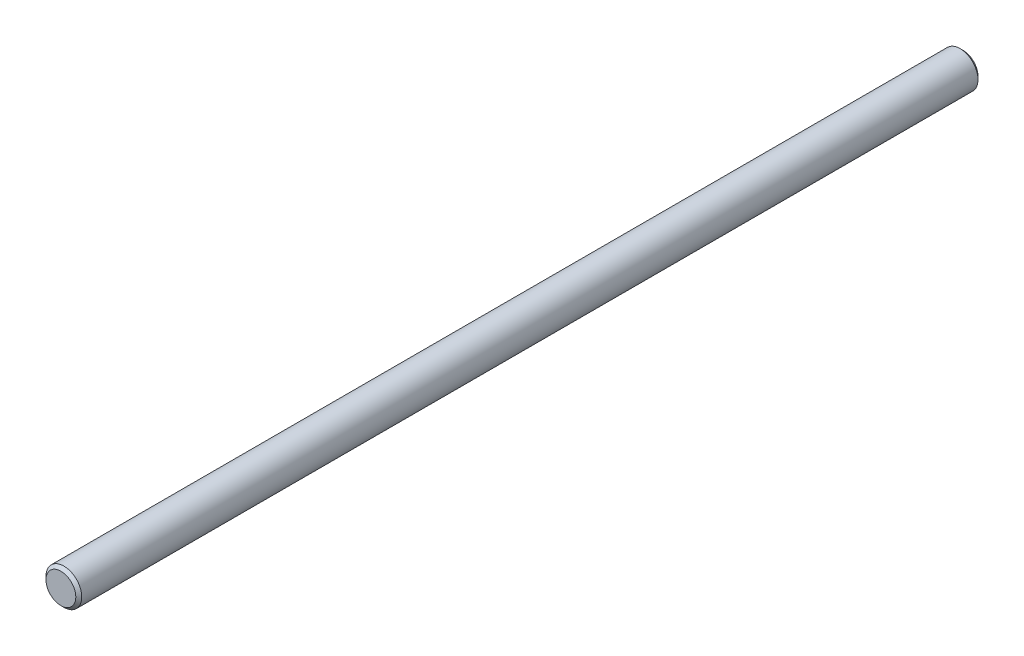
SolidWorks part; units mm, degrees
ref_plane "Front Plane" through (0, 0, 0) normal (0, 0, 1) x (1, 0, 0)
ref_plane "Top Plane" through (0, 0, 0) normal (0, 1, 0) x (1, 0, 0)
ref_plane "Right Plane" through (0, 0, 0) normal (1, 0, 0) x (0, 0, -1)
sketch "Sketch1" plane through (0, 0, 0) normal (0, 0, 1) x (1, 0, 0)
  circle A0 centre (0, 0) radius 6
  dimension "D1" = 12
extrude "Boss-Extrude1" add sketch "Sketch1" along normal mid plane 302.5
chamfer "Chamfer1" distance 1 angle 45 2 edges at (6, 0, -151.25) (6, 0, 151.25)
